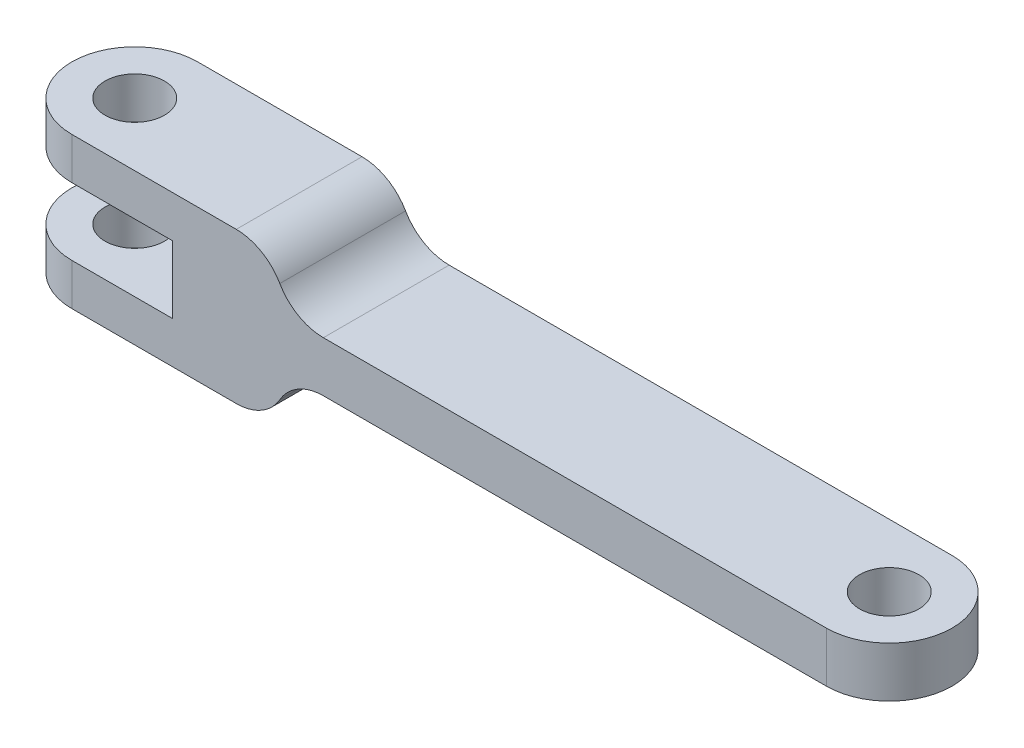
SolidWorks part; units mm, degrees
ref_plane "Front Plane" through (0, 0, 0) normal (0, 0, 1) x (1, 0, 0)
ref_plane "Top Plane" through (0, 0, 0) normal (0, 1, 0) x (1, 0, 0)
ref_plane "Right Plane" through (0, 0, 0) normal (1, 0, 0) x (0, 0, -1)
sketch "Sketch1" plane through (0, 0, 0) normal (0, 1, 0) x (1, 0, 0)
  line L0 (0, 3.175) -> (38.1, 3.175)
  line L1 (38.1, 3.175) -> (38.1, -3.175)
  line L2 (38.1, -3.175) -> (0, -3.175)
  line L3 (19.05, 3.175) -> (19.05, 10.1698) construction
  circle A0 centre (0, 0) radius 3.175
  circle A1 centre (0, 0) radius 1.5
  circle A3 centre (38.1, 0) radius 1.5
  circle A4 centre (38.1, 0) radius 3.175
  point P13 (19.05, 3.175)
  dimension "D1" = 6.35
  dimension "D2" = 3
  dimension "D3" = 38.1
extrude "Boss-Extrude1" add sketch "Sketch1" along normal blind 7.62 contours L2 L3 L0 A0 | L3 L2 A4 L0 | A0 A1 | A4 L1 A3 | A4 L1 A3 | A3 L1 | A3 L1
ref_plane "Plane1" through (0, 3.81, 0) normal (0, 1, 0) x (1, 0, 0)
sketch "Sketch2" plane through (0, 3.81, 0) normal (0, 1, 0) x (1, 0, 0)
  line L0 (0, 3.175) -> (5.08, 3.175)
  line L1 (0, 3.175) -> (38.1, 3.175) construction
  line L2 (5.08, 3.175) -> (5.08, -3.175)
  line L3 (38.1, -3.175) -> (0, -3.175) construction
  line L4 (5.08, -3.175) -> (0, -3.175)
  arc A0 (0, 3.175) -> (0, -3.175) centre (0, 0) ccw construction
  circle A1 centre (0, 0) radius 1.5 construction
  arc A2 (0, 3.175) -> (0, -3.175) centre (0, 0) ccw
  circle A3 centre (0, 0) radius 1.5
  dimension "D1" = 5.08
extrude "Cut-Extrude1" cut sketch "Sketch2" against normal blind 1.7 and the other way blind 1.7
sketch "Sketch3" plane through (0, 7.62, 0) normal (0, 1, 0) x (1, 0, 0)
  line L0 (0, 3.175) -> (38.1, 3.175) construction
  line L1 (10.16, 3.175) -> (44.982, 3.175)
  line L2 (10.16, 3.175) -> (10.16, -7.0305)
  line L3 (10.16, -7.0305) -> (44.982, -7.0305)
  line L4 (44.982, 3.175) -> (44.982, -7.0305)
  point P6 (44.982, -3.1145)
  dimension "D1" = 10.16
extrude "Cut-Extrude2" cut sketch "Sketch3" against normal blind 2.54
mirror "Mirror1" about plane through (0, 3.81, 0) normal (0, 1, 0) of "Cut-Extrude2"
fillet "Fillet1" radius 2.54 2 edges at (10.16, 5.08, 0) (10.16, 2.54, 0)
fillet "Fillet2" radius 2.54 2 edges at (10.16, 7.62, 0) (10.16, 0, 0)
